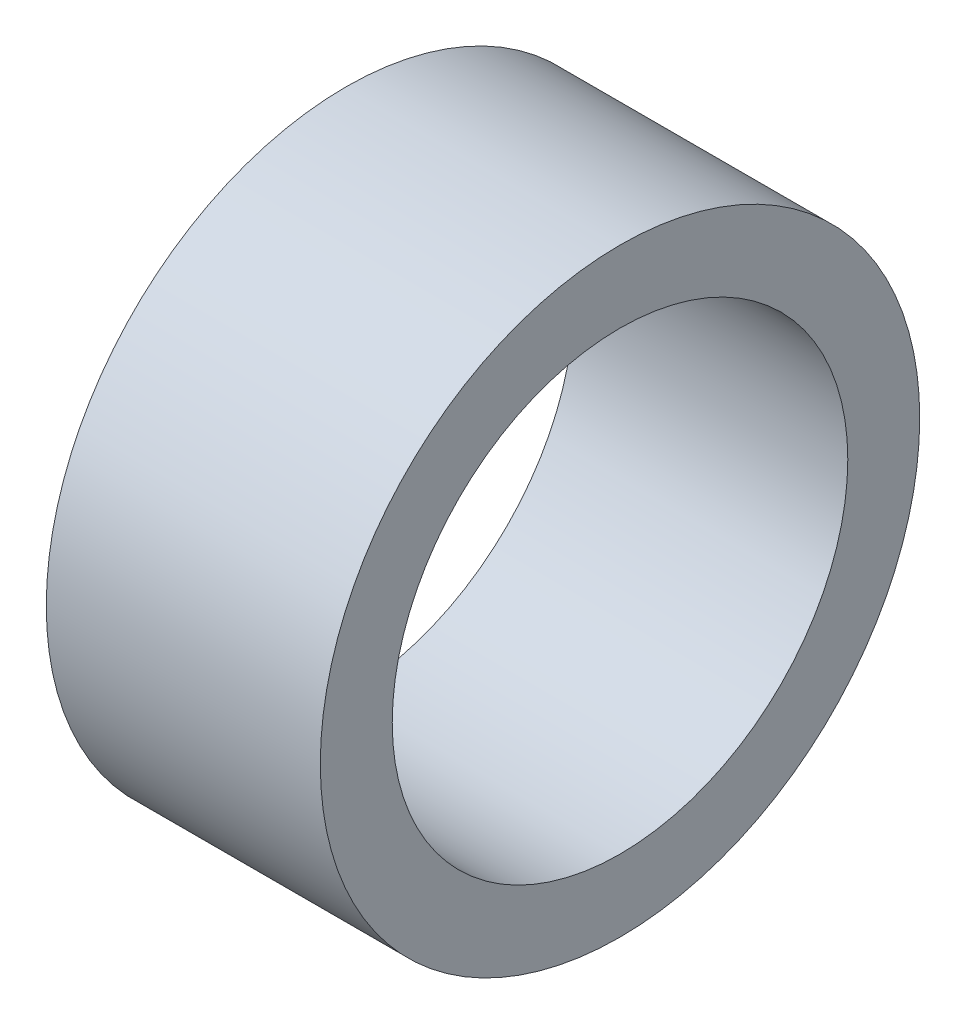
SolidWorks part; units mm, degrees
material "Nylon 6/10"
ref_plane "Front Plane" through (0, 0, 0) normal (0, 0, 1) x (1, 0, 0)
ref_plane "Top Plane" through (0, 0, 0) normal (0, 1, 0) x (1, 0, 0)
ref_plane "Right Plane" through (0, 0, 0) normal (1, 0, 0) x (0, 0, -1)
sketch "Sketch1" plane through (0, 0, 0) normal (0, 0, 1) x (1, 0, 0)
  line L0 (31.75, -13.8602) -> (31.75, 12.314) construction
  line L1 (31.75, 5.5562) -> (36.83, 5.5562)
  line L2 (31.75, 5.5562) -> (31.75, 4.2227)
  line L3 (31.75, 4.2227) -> (36.83, 4.2227)
  line L4 (36.83, 5.5562) -> (36.83, 4.2227)
  line L5 (0, 0) -> (42.6651, 0) construction
  line L7 (50.5354, 3.9687) -> (-48.4378, 3.9688) construction
  dimension "D1" = 0.254
  dimension "D2" = 11.1125
  dimension "D3" = 5.08
revolve "Revolve1" add sketch "Sketch1" angle 360 about L5
